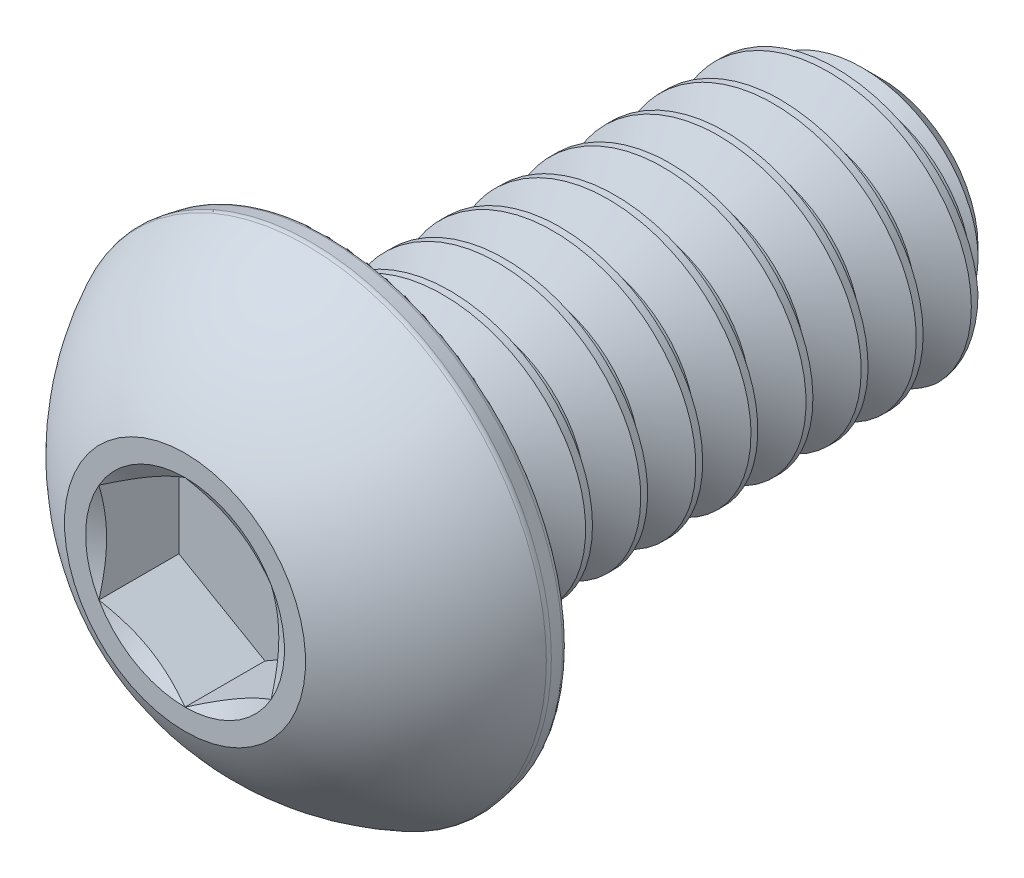
SolidWorks part; units mm, degrees
ref_plane "Front Plane" through (0, 0, 0) normal (0, 0, 1) x (1, 0, 0)
ref_plane "Top Plane" through (0, 0, 0) normal (0, 1, 0) x (1, 0, 0)
ref_plane "Right Plane" through (0, 0, 0) normal (1, 0, 0) x (0, 0, -1)
sketch "Sketch1" plane through (0, 0, 0) normal (1, 0, 0) x (0, 0, -1)
  line L0 (-8.0264, 0) -> (8.0264, 0) construction
  line L1 (-8.0264, 0) -> (-8.0264, 5.5499)
  line L2 (-8.0264, 5.5499) -> (-4.6736, 5.5499)
  line L3 (-4.6736, 5.5499) -> (-4.6736, 3.175)
  line L4 (-4.6736, 3.175) -> (8.0264, 3.175)
  line L5 (8.0264, 3.175) -> (8.0264, 0)
  point P2 (0, 0)
  point P4 (6.7564, 0)
  point P9 (6.1214, 3.175)
  point P10 (6.1214, -3.175)
  point P11 (8.0264, -3.175)
  point P15 (-6.1824, 0)
  dimension "Head Height" = 3.3528
  dimension "Head Diameter" = 11.0998
  dimension "Length" = 12.7
  dimension "Screw Size Decimal Equivalent" = 6.35
  dimension "Thread Pitch" = 1.27
  dimension "D1" = 1.905
  dimension "D2" = 1.844
sketch "Sketch2" plane through (0, 0, 0) normal (0, 0, 1) x (1, 0, 0)
  line L0 (0, 3.175) -> (0, 0) construction
  line L1 (0, 2.2914) -> (-1.9844, 1.1457)
  line L2 (-1.9844, 1.1457) -> (-1.9844, -1.1457)
  line L3 (-1.9844, -1.1457) -> (0, -2.2914)
  line L4 (0, -2.2914) -> (1.9844, -1.1457)
  line L5 (1.9844, -1.1457) -> (1.9844, 1.1457)
  line L6 (1.9844, 1.1457) -> (0, 2.2914)
  circle A0 centre (0, 0) radius 1.9844 construction
  circle A1 centre (0, 0) radius 2.7781
  point P10 (0, 2.7781)
  dimension "D1" = 5.5563
  dimension "Drive Size" = 3.9688
sketch "Sketch3" plane through (0, 0, 0) normal (1, 0, 0) x (0, 0, -1)
  line L0 (-8.0264, 0) -> (-8.0264, 2.7781)
  line L1 (-8.0264, 0) -> (-8.0264, 5.5499) construction
  line L2 (-8.0264, 5.5499) -> (-4.6736, 5.5499) construction
  line L3 (-5.1765, 5.5499) -> (-4.6736, 5.4612)
  line L4 (-4.6736, 5.5499) -> (-4.6736, 3.175) construction
  line L5 (-4.6736, 5.4612) -> (-4.6736, 3.175)
  line L6 (-8.0264, 0) -> (8.0264, 0) construction
  line L7 (-8.0264, 0) -> (8.0264, 0)
  line L8 (8.0264, 0) -> (8.0264, 2.2225)
  line L9 (8.0264, 3.175) -> (8.0264, 0) construction
  line L10 (8.0264, 2.2225) -> (7.0739, 3.175)
  line L11 (-4.6736, 3.175) -> (8.0264, 3.175) construction
  line L12 (7.0739, 3.175) -> (-4.6736, 3.175)
  arc A0 (-8.0264, 2.7781) -> (-5.1765, 5.5499) centre (-2.5516, 0) cw
  dimension "D1" = 0.5029
  dimension "D2" = 10
  dimension "D3" = 45
  dimension "D4" = 0.9525
revolve "Revolve1" add sketch "Sketch3" angle 360 about L7
sketch "Sketch4" plane through (0, 0, 8.0264) normal (0, 0, 1) x (1, 0, 0)
  line L0 (-1.9844, -1.1457) -> (0, -2.2914) construction
  line L1 (-1.9844, 1.1457) -> (-1.9844, -1.1457) construction
  line L2 (0, 2.2914) -> (-1.9844, 1.1457) construction
  line L3 (1.9844, 1.1457) -> (0, 2.2914) construction
  line L4 (1.9844, -1.1457) -> (1.9844, 1.1457) construction
  line L5 (0, -2.2914) -> (1.9844, -1.1457) construction
  line L6 (-1.9844, -1.1457) -> (0, -2.2914)
  line L7 (-1.9844, 1.1457) -> (-1.9844, -1.1457)
  line L8 (0, 2.2914) -> (-1.9844, 1.1457)
  line L9 (1.9844, 1.1457) -> (0, 2.2914)
  line L10 (1.9844, -1.1457) -> (1.9844, 1.1457)
  line L11 (0, -2.2914) -> (1.9844, -1.1457)
extrude "Cut-Extrude1" cut sketch "Sketch4" against normal up to vertex (1.844 mm away) up to point (0, 0, 6.1824)
sketch "Sketch5" plane through (0, 0, 8.0264) normal (0, 0, 1) x (1, 0, 0)
  circle A0 centre (0, 0) radius 2.2914
extrude "Cut-Extrude2" cut sketch "Sketch5" against normal up to vertex (1.844 mm away) draft 60 up to point (0, 0, 6.1824)
fillet "Fillet1" radius 0.1676 2 edges at (5.5499, 0, 5.1765) (5.4612, 0, 4.6736)
split "Split1" bodies to split 106 resulting bodies 107 108 split by face at (5.3206, 0, 4.6736)
sketch "Sketch6" plane through (0, 0, -8.0264) normal (0, 0, -1) x (-1, 0, 0)
  circle A0 centre (0, 0) radius 3.175 construction
  circle A1 centre (0, 0) radius 3.175
curve "Helix/Spiral1" pitch 1.27 height 13.97 radius 3.175 centre (0, 0, -8.0264) axis (0, 0, 1) start towards (0, 1, 0)
sketch "Sketch7" plane through (0, 0, 0) normal (1, 0, 0) x (0, 0, -1)
  line L0 (7.947, 3.3125) -> (8.582, 2.2126) construction
  line L1 (8.582, 2.2126) -> (9.217, 3.3125) construction
  line L2 (9.217, 3.3125) -> (7.947, 3.3125) construction
  line L3 (7.9867, 3.2437) -> (9.1773, 3.2437)
  line L4 (9.1773, 3.2437) -> (8.6614, 2.3501)
  line L5 (8.6614, 2.3501) -> (8.5027, 2.3501)
  line L6 (8.5027, 2.3501) -> (7.9867, 3.2437)
  line L7 (8.582, 2.3501) -> (8.582, 2.2126) construction
  line L8 (8.0264, 3.175) -> (9.1377, 3.175) construction
  line L9 (8.582, 3.3125) -> (8.582, 3.175) construction
  point P12 (8.582, 3.2437)
  dimension "D1" = 1.27
  dimension "D2" = 0.1588
sweep "Cut-Sweep1" cut profiles "Sketch7" path "Helix/Spiral1" align with end faces yes
sketch "Sketch8" plane through (0, 0, 4.6736) normal (0, 0, -1) x (-1, 0, 0)
  circle A0 centre (0, 0) radius 3.3125
extrude "Boss-Extrude1" add sketch "Sketch8" along normal up to vertex (10.795 mm away) draft 45 up to point (0, 3.175, -6.1214)
equation "\"D1@Sketch1\"=\"Thread Pitch@Sketch1\"*1.5"
equation "\"D2@Sketch1\"=0.55*\"Head Height@Sketch1\""
equation "\"D1@Sketch2\"=\"Drive Size@Sketch2\"*1.4"
equation "\"D1@Sketch3\"=0.15*\"Head Height@Sketch1\""
equation "\"D4@Sketch3\"=0.75*\"Thread Pitch@Sketch1\""
equation "\"D1@Fillet1\"=.05*\"Head Height@Sketch1\""
equation "\"D4@Helix/Spiral1\"=\"Thread Pitch@Sketch1\""
equation "\"D3@Helix/Spiral1\"=\"Length@Sketch1\"+\"Thread Pitch@Sketch1\""
equation "\"D2@Sketch7\"=\"D1@Sketch7\"/8"
equation "\"D1@Sketch7\"=\"Thread Pitch@Sketch1\""
